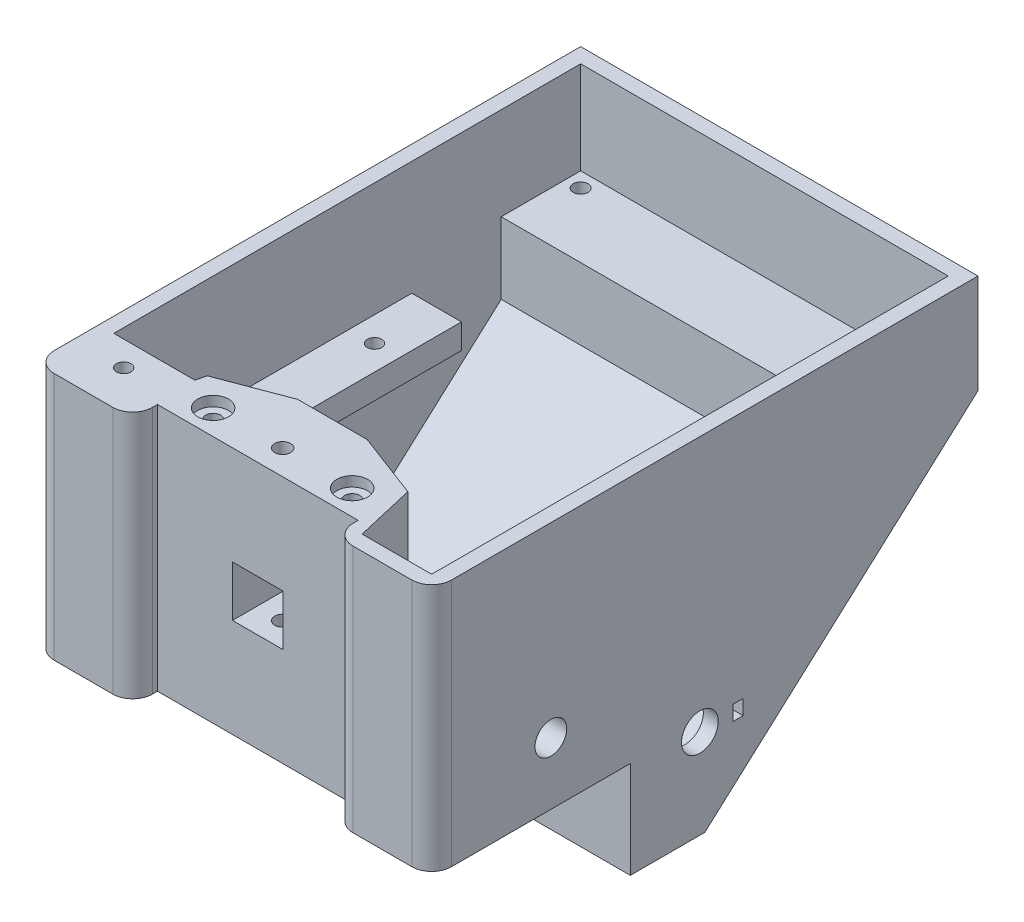
SolidWorks part; units mm, degrees
ref_plane "Спереди" through (0, 0, 0) normal (0, 0, 1) x (1, 0, 0)
ref_plane "Сверху" through (0, 0, 0) normal (0, 1, 0) x (1, 0, 0)
ref_plane "Справа" through (0, 0, 0) normal (1, 0, 0) x (0, 0, -1)
sketch "Sketch2" plane through (0, 0, 0) normal (1, 0, 0) x (0, 0, -1)
  line L0 (-27.3205, 20.9982) -> (-27.3205, -29.0018)
  line L1 (-27.3205, -29.0018) -> (12.6795, -29.0018)
  line L2 (12.6795, -29.0018) -> (12.6795, -48.5114)
  line L3 (12.6795, -48.5114) -> (27.6795, -48.5114)
  line L4 (82.6795, 20.9982) -> (82.6795, 0.9982)
  line L5 (82.6795, 20.9982) -> (-27.3205, 20.9982)
  line L6 (82.6795, 0.9982) -> (27.6795, -48.5114)
  dimension "D1" = 110
  dimension "D2" = 50
  dimension "D3" = 40
  dimension "D4" = 15
  dimension "D5" = 20
extrude "Boss-Extrude1" add sketch "Sketch2" along normal blind 80
shell "Shell1" thickness 3 removed face at (40, 20.9982, -27.6795)
sketch "Sketch3" plane through (0, 0, 24.3205) normal (0, 0, -1) x (-1, 0, 0)
  line L0 (-40, 20.9982) -> (-40, -26.0018) construction
  line L3 (-77, 20.9982) -> (-3, 20.9982) construction
  line L4 (-77, -26.0018) -> (-3, -26.0018) construction
  line L6 (-17, 20.9982) -> (-63, 20.9982)
  line L7 (-17, 20.9982) -> (-17, -26.0018)
  line L8 (-17, -26.0018) -> (-63, -26.0018)
  line L9 (-63, 20.9982) -> (-63, -26.0018)
  line L10 (-17, 20.9982) -> (-63, -26.0018) construction
  line L11 (-17, -26.0018) -> (-63, 20.9982) construction
  point P6 (-40, -2.5018)
  dimension "D1" = 46
extrude "Boss-Extrude2" add sketch "Sketch3" along normal blind 17
sketch "Sketch4" plane through (0, 0, 27.3205) normal (0, 0, 1) x (1, 0, 0)
  line L0 (0, 20.9982) -> (80, -29.0018) construction
  line L2 (45.1, -9.1018) -> (34.9, -9.1018)
  line L3 (45.1, -9.1018) -> (45.1, 1.0982)
  line L4 (45.1, 1.0982) -> (34.9, 1.0982)
  line L5 (34.9, -9.1018) -> (34.9, 1.0982)
  line L6 (45.1, -9.1018) -> (34.9, 1.0982) construction
  line L7 (45.1, 1.0982) -> (34.9, -9.1018) construction
  point P4 (40, -4.0018)
  dimension "D1" = 10.2
extrude "Cut-Extrude1" cut sketch "Sketch4" against normal up to surface (20 mm away) up to face at (40, -2.5018, 7.3205)
sketch "Sketch6" plane through (0, -29.0018, 0) normal (0, -1, 0) x (1, 0, 0)
  line L0 (40, 27.3205) -> (40, -12.6795) construction
  line L1 (47.5, -5.4795) -> (32.5, -5.4795)
  line L2 (47.5, -5.4795) -> (47.5, 7.3205)
  line L3 (47.5, 7.3205) -> (32.5, 7.3205)
  line L4 (32.5, -5.4795) -> (32.5, 7.3205)
  line L5 (47.5, -5.4795) -> (32.5, 7.3205) construction
  line L6 (47.5, 7.3205) -> (32.5, -5.4795) construction
  line L7 (80, -12.6795) -> (0, -12.6795) construction
  line L9 (80, 27.3205) -> (0, 27.3205) construction
  point P0 (40, 0.9205)
  dimension "D1" = 15
  dimension "D2" = 12.8
  dimension "D4" = 20
extrude "Cut-Extrude2" cut sketch "Sketch6" against normal up to surface (3 mm away) up to face at (40, -26.0018, 10.0705)
sketch "Sketch7" plane through (0, 0, 27.3205) normal (0, 0, 1) x (1, 0, 0)
  line L0 (40, 20.9982) -> (40, -29.0018) construction
  line L1 (80, 20.9982) -> (0, 20.9982) construction
  line L2 (80, -29.0018) -> (0, -29.0018) construction
  line L4 (60.2, -29.0018) -> (19.8, -29.0018)
  line L5 (60.2, -29.0018) -> (60.2, 20.9982)
  line L6 (60.2, 20.9982) -> (19.8, 20.9982)
  line L7 (19.8, -29.0018) -> (19.8, 20.9982)
  line L8 (60.2, -29.0018) -> (19.8, 20.9982) construction
  line L9 (60.2, 20.9982) -> (19.8, -29.0018) construction
  point P6 (40, -4.0018)
  dimension "D1" = 40.4
extrude "Cut-Extrude3" cut sketch "Sketch7" against normal blind 5
fillet "Fillet1" radius 4 4 edges at (19.8, -4.0018, 27.3205) (60.2, -4.0018, 27.3205) (80, -4.0018, 27.3205) (0, -4.0018, 27.3205)
sketch "Sketch12" plane through (0, 20.9982, 0) normal (0, 1, 0) x (1, 0, 0)
  line L0 (19.8, -22.3205) -> (19.8, -12.3205) construction
  line L1 (19.8, -12.3205) -> (60.2, -12.3205) construction
  line L2 (60.2, -12.3205) -> (60.2, -22.3205) construction
  line L3 (33, -7.3205) -> (19.8, -12.3205)
  line L4 (17, -7.3205) -> (63, -7.3205) construction
  line L5 (19.8, -12.3205) -> (17, -24.3205)
  line L6 (17, -24.3205) -> (17, -7.3205)
  line L7 (17, -7.3205) -> (33, -7.3205)
  line L8 (47, -7.3205) -> (63, -7.3205)
  line L9 (63, -7.3205) -> (63, -24.3205)
  line L10 (63, -24.3205) -> (60.2, -12.3205)
  line L11 (60.2, -12.3205) -> (47, -7.3205)
  dimension "D1" = 10
  dimension "D2" = 16
extrude "Cut-Extrude7" cut sketch "Sketch12" against normal up to surface (47 mm away) up to face at (40, -26.0018, 7.0205)
sketch "Sketch13" plane through (0, 20.9982, 0) normal (0, 1, 0) x (1, 0, 0)
  line L0 (19.8, -22.3205) -> (19.8, -12.3205) construction
  line L1 (19.8, -12.3205) -> (60.2, -12.3205) construction
  line L2 (60.2, -12.3205) -> (60.2, -22.3205) construction
  line L3 (60.2, -17.3205) -> (19.8, -17.3205) construction
  circle A0 centre (26, -17.3205) radius 1.5
  circle A1 centre (54, -17.3205) radius 1.5
  point P14 (40, -17.3205)
  dimension "D1" = 3
  dimension "D2" = 28
  dimension "D3" = 14
  dimension "D4" = 6.2
extrude "Cut-Extrude8" cut sketch "Sketch13" against normal blind 25
sketch "Sketch14" plane through (0, 20.9982, 0) normal (0, 1, 0) x (1, 0, 0)
  circle A0 centre (26, -17.3205) radius 3.1
  circle A1 centre (54, -17.3205) radius 3.1
  dimension "D1" = 6.2
extrude "Cut-Extrude9" cut sketch "Sketch14" against normal blind 2
sketch "Sketch17" plane through (77, 0, 0) normal (-1, 0, 0) x (0, 0, 1)
  line L0 (-45.6795, -2.0018) -> (-0.6795, -2.0018)
  line L1 (-0.6795, -2.0018) -> (-0.6795, -7.0018)
  line L2 (-0.6795, -7.0018) -> (-45.6795, -7.0018)
  line L3 (-45.6795, -7.0018) -> (-45.6795, -2.0018)
  line L4 (-79.6795, 20.9982) -> (24.3205, 20.9982) construction
  line L5 (-79.6795, 2.3342) -> (-79.6795, 20.9982) construction
  dimension "D1" = 45
  dimension "D2" = 5
  dimension "D3" = 23
  dimension "D4" = 34
extrude "Boss-Extrude5" add sketch "Sketch17" along normal up to surface (74 mm away) up to face at (3, -14.0994, -24.0865)
sketch "Sketch18" plane through (0, -2.0018, 0) normal (0, 1, 0) x (1, 0, 0)
  line L0 (40, 0.6795) -> (40, 45.6795) construction
  line L1 (3, 0.6795) -> (77, 0.6795) construction
  line L2 (3, 45.6795) -> (77, 45.6795) construction
  line L3 (77, 0.6795) -> (77, 45.6795) construction
  line L4 (13, 0.6795) -> (67, 0.6795)
  line L5 (13, 0.6795) -> (13, 45.6795)
  line L6 (13, 45.6795) -> (67, 45.6795)
  line L7 (67, 0.6795) -> (67, 45.6795)
  line L8 (13, 0.6795) -> (67, 45.6795) construction
  line L9 (13, 45.6795) -> (67, 0.6795) construction
  point P6 (40, 23.1795)
  dimension "D1" = 10
extrude "Cut-Extrude10" cut sketch "Sketch18" against normal up to next
sketch "Sketch19" plane through (0, -2.0018, 0) normal (0, 1, 0) x (1, 0, 0)
  line L0 (72, 45.6795) -> (72, 0.6795) construction
  line L1 (67, 45.6795) -> (77, 45.6795) construction
  line L2 (67, 0.6795) -> (77, 0.6795) construction
  line L3 (8, 45.6795) -> (8, 0.6795) construction
  line L4 (3, 45.6795) -> (13, 45.6795) construction
  line L5 (3, 0.6795) -> (13, 0.6795) construction
  circle A0 centre (72, 37.1795) radius 1.45
  circle A1 centre (72, 6.1795) radius 1.45
  circle A2 centre (8, 33.1795) radius 1.45
  circle A3 centre (8, 6.1795) radius 1.45
  point P20 (72, 23.1795)
  point P21 (8, 23.1795)
  dimension "D1" = 2.9
  dimension "D2" = 14
  dimension "D3" = 17
  dimension "D4" = 17
  dimension "D5" = 10
extrude "Cut-Extrude11" cut sketch "Sketch19" against normal up to next
sketch "Sketch21" plane through (0, -26.0018, 0) normal (0, 1, 0) x (1, 0, 0)
  line L0 (3, -24.3205) -> (3, -14.3205)
  line L1 (3, -24.3205) -> (3, 15.6795) construction
  line L2 (3, -14.3205) -> (19.3333, -14.3205)
  line L3 (19.8, -12.3205) -> (17, -24.3205) construction
  line L4 (19.3333, -14.3205) -> (17, -24.3205)
  line L6 (3, -24.3205) -> (17, -24.3205)
  dimension "D1" = 10
extrude "Boss-Extrude6" add sketch "Sketch21" along normal up to surface (47 mm away) up to face at (54, 20.9982, 20.4205)
sketch "Sketch22" plane through (0, 20.9982, 0) normal (0, 1, 0) x (1, 0, 0)
  line L0 (0, 82.6795) -> (0, -23.3205) construction
  line L1 (15.8, -27.3205) -> (4, -27.3205) construction
  circle A0 centre (10, -19.3205) radius 1.45
  dimension "D1" = 2.9
  dimension "D2" = 10
  dimension "D3" = 8
extrude "Cut-Extrude12" cut sketch "Sketch22" against normal through all
sketch "Sketch24" plane through (80, 0, 0) normal (1, 0, 0) x (0, 0, -1)
  line L0 (12.6795, -48.5114) -> (27.6795, -48.5114) construction
  line L1 (12.6795, -29.0018) -> (12.6795, -48.5114) construction
  line L2 (18.1795, -30.5114) -> (18.1795, -19.0114) construction
  line L3 (18.1795, -19.0114) -> (35.1795, -19.0114) construction
  line L4 (35.1795, -19.0114) -> (35.1795, -30.5114) construction
  line L5 (26.6795, -19.0114) -> (26.6795, -39.0114) construction
  line L6 (30.3795, -30.5114) -> (34.3795, -30.5114) construction
  line L8 (33.3795, -32.0114) -> (35.3795, -32.0114)
  line L9 (33.3795, -32.0114) -> (33.3795, -29.0114)
  line L10 (33.3795, -29.0114) -> (35.3795, -29.0114)
  line L11 (35.3795, -32.0114) -> (35.3795, -29.0114)
  line L12 (33.3795, -32.0114) -> (35.3795, -29.0114) construction
  line L13 (33.3795, -29.0114) -> (35.3795, -32.0114) construction
  circle A0 centre (26.6795, -30.5114) radius 3.7
  circle A1 centre (26.6795, -30.5114) radius 8.5 construction
  dimension "D1" = 7.4
  dimension "D2" = 17
  dimension "D3" = 18
  dimension "D4" = 14
  dimension "D5" = 20
  dimension "D6" = 4
  dimension "D7" = 2
  dimension "D8" = 3
extrude "Cut-Extrude13" cut sketch "Sketch24" against normal up to next
sketch "Sketch26" plane through (3, 0, 0) normal (1, 0, 0) x (0, 0, -1)
  line L0 (79.6795, 2.3342) -> (63.6795, 2.3342)
  line L1 (63.6795, 2.3342) -> (63.6795, -12.0686)
  line L2 (26.5281, -45.5114) -> (79.6795, 2.3342) construction
  line L3 (63.6795, -12.0686) -> (79.6795, 2.3342)
  dimension "D1" = 16
extrude "Boss-Extrude7" add sketch "Sketch26" along normal up to surface (74 mm away) up to face at (77, -30.5114, -34.3795)
sketch "Sketch27" plane through (0, 2.3342, 0) normal (0, 1, 0) x (1, 0, 0)
  line L0 (3, 76.6795) -> (77, 76.6795) construction
  line L1 (3, 79.6795) -> (3, 63.6795) construction
  line L2 (77, 79.6795) -> (77, 63.6795) construction
  line L3 (80, 82.6795) -> (0, 82.6795) construction
  circle A0 centre (6, 76.6795) radius 1.5
  circle A1 centre (74, 76.6795) radius 1.5
  point P10 (40, 76.6795)
  dimension "D1" = 3
  dimension "D2" = 68
  dimension "D3" = 34
  dimension "D4" = 6
extrude "Cut-Extrude14" cut sketch "Sketch27" against normal blind 10
sketch "Sketch28" plane through (0, 2.3342, 0) normal (0, 1, 0) x (1, 0, 0)
  line L1 (74, 79.9295) -> (71.1854, 78.3045)
  line L2 (71.1854, 78.3045) -> (71.1854, 75.0545)
  line L3 (71.1854, 75.0545) -> (74, 73.4295)
  line L4 (74, 73.4295) -> (76.8146, 75.0545)
  line L5 (76.8146, 75.0545) -> (76.8146, 78.3045)
  line L6 (76.8146, 78.3045) -> (74, 79.9295)
  line L7 (6, 73.4295) -> (8.8146, 75.0545)
  line L8 (8.8146, 75.0545) -> (8.8146, 78.3045)
  line L9 (8.8146, 78.3045) -> (6, 79.9295)
  line L10 (6, 79.9295) -> (3.1854, 78.3045)
  line L11 (3.1854, 78.3045) -> (3.1854, 75.0545)
  line L12 (3.1854, 75.0545) -> (6, 73.4295)
  circle A0 centre (74, 76.6795) radius 3.25 construction
  circle A1 centre (6, 76.6795) radius 3.25 construction
  dimension "D1" = 6.5
extrude "Cut-Extrude15" cut sketch "Sketch28" against normal blind 32 from offset 3 offset against normal yes
sketch "Sketch29" plane through (0, -29.0018, 0) normal (0, -1, 0) x (1, 0, 0)
  line L0 (0, 23.3205) -> (0, -12.6795) construction
  line L1 (7.1854, 17.6955) -> (10, 16.0705)
  line L2 (10, 16.0705) -> (12.8146, 17.6955)
  line L3 (12.8146, 17.6955) -> (12.8146, 20.9455)
  line L4 (12.8146, 20.9455) -> (10, 22.5705)
  line L5 (10, 22.5705) -> (7.1854, 20.9455)
  line L6 (7.1854, 20.9455) -> (7.1854, 17.6955)
  circle A0 centre (10, 19.3205) radius 3.25 construction
  dimension "D1" = 6.5
extrude "Cut-Extrude16" cut sketch "Sketch29" against normal blind 30
sketch "Sketch30" plane through (0, -26.0018, 0) normal (0, 1, 0) x (1, 0, 0)
  line L0 (77, -24.3205) -> (63, -24.3205)
  line L1 (63, -24.3205) -> (60.2, -12.3205)
  line L2 (63, -24.3205) -> (60.2, -12.3205) construction
  line L3 (60.2, -12.3205) -> (77, -12.3205)
  line L4 (77, -24.3205) -> (77, 15.6795) construction
  line L5 (77, -12.3205) -> (77, -24.3205)
  dimension "D1" = 12
extrude "Boss-Extrude8" add sketch "Sketch30" along normal blind 20
sketch "Sketch31" plane through (0, -6.0018, 0) normal (0, 1, 0) x (1, 0, 0)
  line L0 (76, -27.3205) -> (64.2, -27.3205) construction
  line L1 (80, -23.3205) -> (80, 12.6795) construction
  circle A0 centre (72, -21.3205) radius 1.5
  dimension "D3" = 3
  dimension "D1" = 6
  dimension "D2" = 8
extrude "Cut-Extrude17" cut sketch "Sketch31" against normal through all
sketch "Sketch32" plane through (0, -29.0018, 0) normal (0, -1, 0) x (1, 0, 0)
  line L1 (72, 24.5705) -> (69.1854, 22.9455)
  line L2 (69.1854, 22.9455) -> (69.1854, 19.6955)
  line L3 (69.1854, 19.6955) -> (72, 18.0705)
  line L4 (72, 18.0705) -> (74.8146, 19.6955)
  line L5 (74.8146, 19.6955) -> (74.8146, 22.9455)
  line L6 (74.8146, 22.9455) -> (72, 24.5705)
  circle A0 centre (72, 21.3205) radius 3.25 construction
  dimension "D1" = 6.5
extrude "Cut-Extrude18" cut sketch "Sketch32" against normal blind 15
sketch "Sketch33" plane through (0, -2.0018, 0) normal (0, 1, 0) x (1, 0, 0)
  line L0 (67, 40.6795) -> (77, 40.6795)
  line L1 (67, 0.6795) -> (67, 45.6795) construction
  line L2 (77, 0.6795) -> (77, 45.6795) construction
  line L3 (77, 40.6795) -> (77, 45.6795)
  line L4 (77, 45.6795) -> (67, 45.6795)
  line L5 (67, 45.6795) -> (67, 40.6795)
  dimension "D1" = 5
extrude "Cut-Extrude19" cut sketch "Sketch33" against normal up to next
sketch "Sketch34" plane through (0, 20.9982, 0) normal (0, 1, 0) x (1, 0, 0)
  line L0 (54, -17.3205) -> (26, -17.3205) construction
  circle A0 centre (40, -17.3205) radius 1.6
  dimension "D1" = 3.2
extrude "Cut-Extrude20" cut sketch "Sketch34" against normal through all
sketch "Sketch36" plane through (0, -29.0018, 0) normal (0, -1, 0) x (1, 0, 0)
  line L1 (38.375, 20.1351) -> (36.75, 17.3205)
  line L2 (36.75, 17.3205) -> (38.375, 14.5059)
  line L3 (38.375, 14.5059) -> (41.625, 14.5059)
  line L4 (41.625, 14.5059) -> (43.25, 17.3205)
  line L5 (43.25, 17.3205) -> (41.625, 20.1351)
  line L6 (41.625, 20.1351) -> (38.375, 20.1351)
  circle A0 centre (40, 17.3205) radius 3.25 construction
  dimension "D1" = 6.5
extrude "Cut-Extrude22" cut sketch "Sketch36" against normal blind 14
sketch "Sketch37" plane through (80, 0, 0) normal (1, 0, 0) x (0, 0, -1)
  line L0 (-23.3205, -16.5114) -> (63.2281, -16.5114) construction
  line L1 (-23.3205, 20.9982) -> (-23.3205, -29.0018) construction
  line L2 (27.6795, -48.5114) -> (82.6795, 0.9982) construction
  line L3 (30.3795, -30.5114) -> (22.9795, -30.5114) construction
  circle A0 centre (-3.3205, -16.5114) radius 3.2
  circle A1 centre (26.6795, -30.5114) radius 3.7 construction
  point P14 (26.6795, -30.5114)
  dimension "D1" = 6.4
  dimension "D2" = 14
  dimension "D3" = 20
extrude "Cut-Extrude23" cut sketch "Sketch37" against normal up to next
sketch "Sketch38" plane through (77, 0, 0) normal (-1, 0, 0) x (0, 0, 1)
  line L0 (12.3205, -26.0018) -> (-15.6795, -26.0018) construction
  line L1 (8.3205, -7.021) -> (-1.6795, -7.021)
  line L2 (8.3205, -7.021) -> (8.3205, -26.0018)
  line L3 (8.3205, -26.0018) -> (-1.6795, -26.0018)
  line L4 (-1.6795, -7.021) -> (-1.6795, -26.0018)
  line L5 (8.3205, -7.021) -> (-1.6795, -26.0018) construction
  line L6 (8.3205, -26.0018) -> (-1.6795, -7.021) construction
  circle A0 centre (3.3205, -16.5114) radius 3.2
  point P0 (3.3205, -16.5114)
  dimension "D1" = 10
extrude "Boss-Extrude9" add sketch "Sketch38" along normal blind 3
sketch "Sketch40" plane through (3, 0, 0) normal (1, 0, 0) x (0, 0, -1)
  line L0 (18.1795, -30.5114) -> (18.1795, -19.0114) construction
  line L1 (18.1795, -19.0114) -> (35.1795, -19.0114) construction
  line L2 (35.1795, -19.0114) -> (35.1795, -30.5114) construction
  line L3 (26.6795, -19.0114) -> (26.6795, -39.0114) construction
  line L4 (30.3795, -30.5114) -> (34.3795, -30.5114) construction
  line L5 (33.3795, -32.0114) -> (35.3795, -32.0114) construction
  line L6 (33.3795, -32.0114) -> (33.3795, -29.0114) construction
  line L7 (33.3795, -29.0114) -> (35.3795, -29.0114) construction
  line L8 (35.3795, -32.0114) -> (35.3795, -29.0114) construction
  line L9 (33.3795, -32.0114) -> (35.3795, -29.0114) construction
  line L10 (33.3795, -29.0114) -> (35.3795, -32.0114) construction
  line L13 (22.9795, -30.5114) -> (18.9795, -30.5114) construction
  line L14 (12.6795, -29.0018) -> (12.6795, -48.5114) construction
  line L15 (17.9795, -29.0114) -> (19.9795, -29.0114)
  line L16 (17.9795, -29.0114) -> (17.9795, -32.0114)
  line L17 (17.9795, -32.0114) -> (19.9795, -32.0114)
  line L18 (19.9795, -29.0114) -> (19.9795, -32.0114)
  line L19 (17.9795, -29.0114) -> (19.9795, -32.0114) construction
  line L20 (17.9795, -32.0114) -> (19.9795, -29.0114) construction
  line L21 (12.6795, -48.5114) -> (27.6795, -48.5114) construction
  circle A0 centre (26.6795, -30.5114) radius 3.7
  circle A1 centre (26.6795, -30.5114) radius 8.5 construction
  dimension "D4" = 17
  dimension "D5" = 17
  dimension "D11" = 7.4
  dimension "D1" = 3
  dimension "D2" = 2
  dimension "D3" = 4
  dimension "D6" = 2
  dimension "D7" = 3
  dimension "D8" = 4
  dimension "D9" = 14
  dimension "D10" = 18
extrude "Cut-Extrude24" cut sketch "Sketch40" against normal up to next
